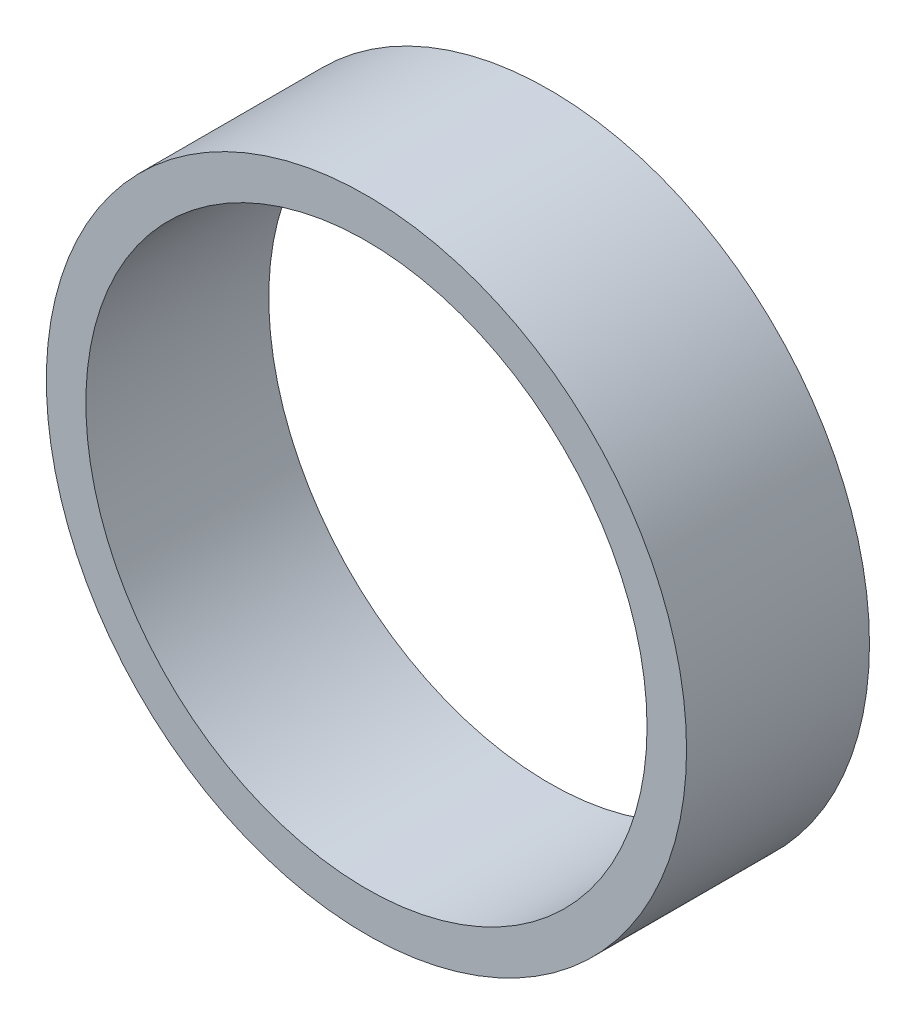
SolidWorks part; units mm, degrees
ref_plane "Plane1" through (0, 0, 0) normal (0, 0, 1) x (1, 0, 0)
ref_plane "Plane2" through (0, 0, 0) normal (0, 1, 0) x (1, 0, 0)
ref_plane "Plane3" through (0, 0, 0) normal (1, 0, 0) x (0, 0, -1)
sketch "Sketch1" plane through (0, 0, 0) normal (0, 0, 1) x (1, 0, 0)
  circle A0 centre (0, 0) radius 38.9636
  circle A1 centre (0, 0) radius 44.45
extrude "BasePipe" add sketch "Sketch1" along normal mid plane 25.4
